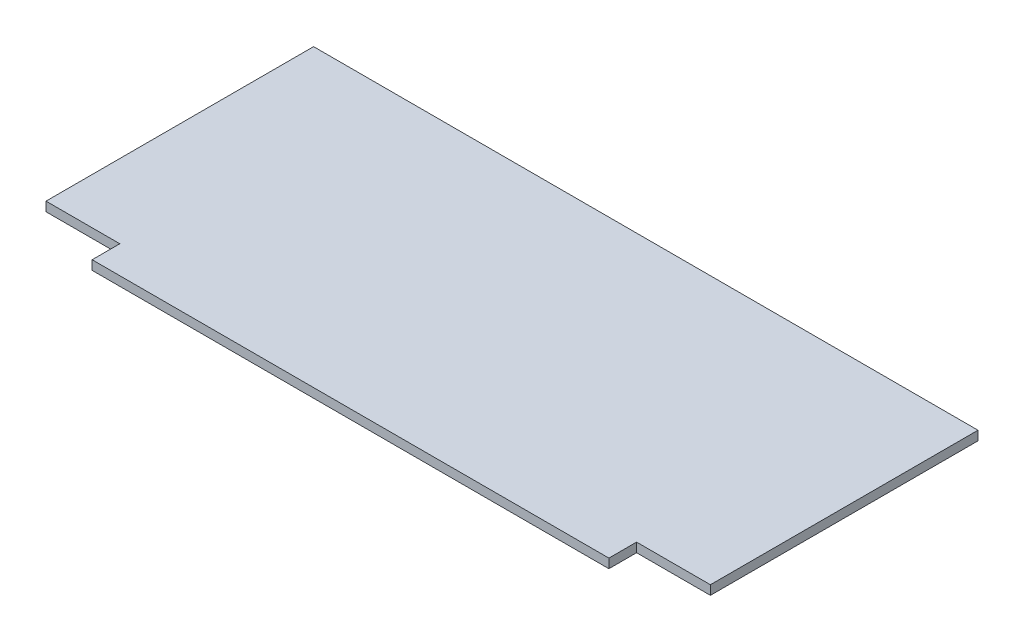
SolidWorks part; units mm, degrees
ref_plane "Front Plane" through (0, 0, 0) normal (0, 0, 1) x (1, 0, 0)
ref_plane "Top Plane" through (0, 0, 0) normal (0, 1, 0) x (1, 0, 0)
ref_plane "Right Plane" through (0, 0, 0) normal (1, 0, 0) x (0, 0, -1)
sketch "Sketch1" plane through (0, 0, 0) normal (0, 1, 0) x (1, 0, 0)
  line L1 (228.6, -101.6) -> (-228.6, -101.6)
  line L2 (228.6, -101.6) -> (228.6, 101.6)
  line L3 (228.6, 101.6) -> (-228.6, 101.6)
  line L4 (-228.6, -101.6) -> (-228.6, 101.6)
  line L5 (228.6, -101.6) -> (-228.6, 101.6) construction
  line L6 (228.6, 101.6) -> (-228.6, -101.6) construction
  point P0 (0, 0)
  dimension "D1" = 457.2
  dimension "D2" = 203.2
extrude "Boss-Extrude1" add sketch "Sketch1" along normal blind 6.35
sketch "Sketch2" plane through (0, 6.35, 0) normal (0, 1, 0) x (1, 0, 0)
  line L1 (-228.6, -101.6) -> (-177.8, -101.6)
  line L2 (-228.6, -101.6) -> (-228.6, -82.55)
  line L3 (-228.6, -82.55) -> (-177.8, -82.55)
  line L4 (-177.8, -101.6) -> (-177.8, -82.55)
  line L5 (228.6, -101.6) -> (177.8, -101.6)
  line L6 (228.6, -101.6) -> (228.6, -82.55)
  line L7 (228.6, -82.55) -> (177.8, -82.55)
  line L8 (177.8, -101.6) -> (177.8, -82.55)
  dimension "D1" = 50.8
  dimension "D2" = 19.05
  dimension "D3" = 19.05
  dimension "D4" = 50.8
extrude "Cut-Extrude1" cut sketch "Sketch2" against normal through all
